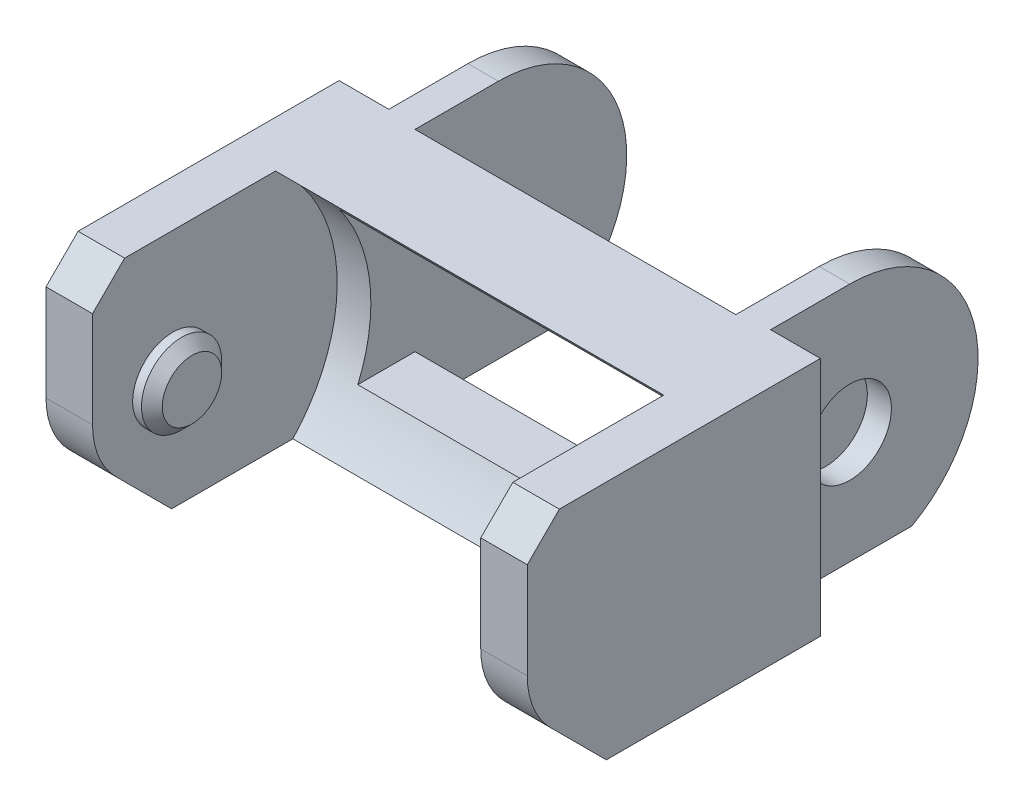
SolidWorks part; units mm, degrees
ref_plane "前基準面" through (0, 0, 0) normal (0, 0, 1) x (1, 0, 0)
ref_plane "上基準面" through (0, 0, 0) normal (0, 1, 0) x (1, 0, 0)
ref_plane "右基準面" through (0, 0, 0) normal (1, 0, 0) x (0, 0, -1)
sketch "草圖1" plane through (0, 0, 0) normal (0, 0, 1) x (1, 0, 0)
  line L1 (-12.751, 5.0503) -> (17.249, 5.0503)
  line L2 (-12.751, 5.0503) -> (-12.751, -9.9497)
  line L3 (-12.751, -9.9497) -> (17.249, -9.9497)
  line L4 (17.249, 5.0503) -> (17.249, -9.9497)
  dimension "D1" = 30
  dimension "D2" = 15
extrude "填料-伸長1" add sketch "草圖1" along normal blind 18
sketch "草圖2" plane through (0, 0, 18) normal (0, 0, 1) x (1, 0, 0)
  line L0 (-12.751, 5.0503) -> (-12.751, -9.9497) construction
  line L1 (-7.751, 3.0503) -> (12.249, 3.0503)
  line L2 (-7.751, 3.0503) -> (-7.751, -6.9497)
  line L3 (-7.751, -6.9497) -> (12.249, -6.9497)
  line L4 (12.249, 3.0503) -> (12.249, -6.9497)
  line L5 (17.249, -9.9497) -> (17.249, 5.0503) construction
  line L6 (17.249, 5.0503) -> (-12.751, 5.0503) construction
  line L7 (-12.751, -9.9497) -> (17.249, -9.9497) construction
  dimension "D1" = 5
  dimension "D2" = 5
  dimension "D3" = 2
  dimension "D4" = 3
extrude "除料-伸長1" cut sketch "草圖2" against normal up to next
sketch "草圖3" plane through (0, -6.9497, 0) normal (0, 1, 0) x (1, 0, 0)
  line L0 (-7.751, 0) -> (-7.751, -18) construction
  line L1 (-7.751, -6) -> (12.249, -6)
  line L2 (-7.751, -6) -> (-7.751, -18)
  line L3 (-7.751, -18) -> (12.249, -18)
  line L4 (12.249, -6) -> (12.249, -18)
  dimension "D1" = 12
extrude "除料-伸長2" cut sketch "草圖3" against normal up to next
sketch "草圖4" plane through (-7.751, 0, 0) normal (1, 0, 0) x (0, 0, -1)
  line L0 (-18, 3.0503) -> (-18, -9.9497) construction
  line L1 (-18, -9.9497) -> (-6, -9.9497) construction
  line L3 (-13, -2.9497) -> (-18, -2.9497)
  line L4 (-13, -2.9497) -> (-13, 7.8945)
  line L5 (-18, -2.9497) -> (-18, 7.8945)
  line L6 (-13, 7.8945) -> (-18, 7.8945)
  circle A0 centre (-13, -2.9497) radius 10.25
  line M3 (0, 3.0503) -> (-18, 3.0503)
  line M4 (-18, 3.0503) -> (-18, -9.9497)
  line M5 (-18, -9.9497) -> (-6, -9.9497)
  line M6 (-6, -9.9497) -> (-6, -6.9497)
  line M7 (-6, -6.9497) -> (0, -6.9497)
  dimension "D2" = 7
  dimension "D3" = 20.5
  dimension "D1" = 5
extrude "除料-伸長5" cut sketch "草圖4" against normal blind 2.1 and the other way blind 22.1 contours L3 L4 M3 M4 | A0 L4 L3 M7 M3 M4 M5 M6 | A0 L4 L6 L5 | A0 L4 M3 | L4 A0 L5 M3 | L5 A0 M7 M6 M5 M4 region at (-7.751, -3.92, 9.9772) region at (-7.751, 0.0503, 15.5) region at (-7.751, -6.4497, 18.275) region at (-7.751, 4.9834, 15.3602) region at (-7.751, 4.7846, 9.7748) region at (-7.751, 7.3136, 16.0262)
sketch "草圖5" plane through (14.349, 0, 0) normal (-1, 0, 0) x (0, 0, 1)
  circle A0 centre (13, -2.9497) radius 2.5
  arc A2 (6.592, 5.0503) -> (5.5125, -9.9497) centre (13, -2.9497) ccw construction
  dimension "D1" = 5
extrude "填料-伸長2" add sketch "草圖5" along normal blind 1.2
sketch "草圖6" plane through (-9.851, 0, 0) normal (1, 0, 0) x (0, 0, -1)
  circle A0 centre (-13, -2.9497) radius 2.5
  arc A1 (-5.5125, -9.9497) -> (-6.592, 5.0503) centre (-13, -2.9497) ccw construction
  dimension "D1" = 5
extrude "填料-伸長3" add sketch "草圖6" along normal blind 1.2
chamfer "導角1" distance 0.65 angle 45 2 edges at (-8.651, -0.4497, 13) (13.149, -5.4497, 13)
sketch "草圖7" plane through (-9.851, 0, 0) normal (1, 0, 0) x (0, 0, -1)
  line L0 (-13.0711, -9.9497) -> (-18, -5.0208)
  line L1 (-18, -9.9497) -> (-5.5125, -9.9497) construction
  line L2 (-18, -9.9497) -> (-18, 5.0503) construction
  circle A0 centre (-13, -2.9497) radius 2.5 construction
  line M4 (-18, 5.0503) -> (-18, -9.9497)
  line M5 (-18, -9.9497) -> (-5.5125, -9.9497)
  dimension "D1" = 45
  dimension "D2" = 5
extrude "除料-伸長6" cut sketch "草圖7" against normal through all both and the other way through all contours L0 M5 M4 region at (-9.851, -8.3067, 16.357)
sketch "草圖8" plane through (-9.851, 0, 0) normal (1, 0, 0) x (0, 0, -1)
  line L0 (-18, -5.0208) -> (-18, -2.9497)
  line L1 (-18, -5.0208) -> (-15.5355, -7.4853)
  line L2 (-13.0711, -9.9497) -> (-18, -5.0208) construction
  circle A0 centre (-13, -2.9497) radius 5
  line M1 (-18, -5.0208) -> (-13.0711, -9.9497)
  line M5 (-18, 5.0503) -> (-18, -5.0208)
extrude "除料-伸長7" cut sketch "草圖8" against normal through all both and the other way through all contours A0 M5 M1 region at (-9.851, -4.8962, 17.6992)
sketch "草圖9" plane through (0, 0, 0) normal (0, 0, -1) x (-1, 0, 0)
  line L0 (-17.249, 5.0503) -> (12.751, 5.0503) construction
  line L1 (-12.249, 5.0503) -> (7.751, 5.0503)
  line L2 (-12.249, 5.0503) -> (-12.249, -9.9497)
  line L3 (-12.249, -9.9497) -> (7.751, -9.9497)
  line L4 (7.751, 5.0503) -> (7.751, -9.9497)
  line L5 (12.751, -9.9497) -> (-17.249, -9.9497) construction
  line L6 (-12.249, 3.0503) -> (-12.249, -6.9497) construction
  line L7 (9.651, -9.9497) -> (-14.149, -9.9497)
  line L8 (9.651, -9.9497) -> (9.651, 5.0503)
  line L9 (9.651, 5.0503) -> (-14.149, 5.0503)
  line L10 (-14.149, -9.9497) -> (-14.149, 5.0503)
  line L11 (7.751, -6.9497) -> (7.751, 3.0503) construction
  line M6 (7.751, 3.0503) -> (7.751, -6.9497)
  line M8 (-12.249, -6.9497) -> (-12.249, 3.0503)
  line M10 (12.751, 5.0503) -> (-17.249, 5.0503)
  line M12 (-17.249, -9.9497) -> (12.751, -9.9497)
  dimension "D1" = 1.9
  dimension "D2" = 1.9
extrude "填料-伸長4" add sketch "草圖9" along normal blind 20 contours L8 L4 M12 M10 M6 | L10 L2 M12 M8 M10 region at (13.199, -2.4497, 0) region at (-8.701, -2.4497, 0)
sketch "草圖10" plane through (14.149, 0, 0) normal (1, 0, 0) x (0, 0, -1)
  line L0 (0, -9.9497) -> (0, 5.0503) construction
  line L1 (20, -9.9497) -> (0, -9.9497) construction
  circle A0 centre (5.2, -2.9497) radius 2.6
  dimension "D1" = 5.2
  dimension "D2" = 5.2
  dimension "D3" = 7
extrude "除料-伸長8" cut sketch "草圖10" against normal through all
sketch "草圖12" plane through (14.149, 0, 0) normal (1, 0, 0) x (0, 0, -1)
  line L1 (5.2, 5.0503) -> (18.304, 5.0503)
  line L2 (5.2, 5.0503) -> (5.2, -15.4926)
  line L3 (5.2, -15.4926) -> (18.304, -15.4926)
  line L4 (18.304, 5.0503) -> (18.304, -15.4926)
  circle A0 centre (5.2, -2.9497) radius 8
  line M3 (0, -9.9497) -> (20, -9.9497)
  line M4 (20, -9.9497) -> (20, 5.0503)
  line M5 (20, 5.0503) -> (0, 5.0503)
extrude "除料-伸長9" cut sketch "草圖12" against normal through all both and the other way through all contours A0 L4 M3 M5 | L4 M5 M3 M4 region at (14.149, -2.1497, -14.8341) region at (14.149, -2.4497, -19.152)
sketch "草圖15" plane through (12.249, 0, 0) normal (1, 0, 0) x (0, 0, -1)
  circle A0 centre (5.2, -2.9497) radius 2.6
extrude "填料-伸長6" add sketch "草圖15" along normal blind 0.4
sketch "草圖16" plane through (-7.751, 0, 0) normal (-1, 0, 0) x (0, 0, 1)
  circle A0 centre (-5.2, -2.9497) radius 2.6
extrude "填料-伸長7" add sketch "草圖16" along normal blind 0.4
chamfer "導角2" distance 2 angle 45 2 edges at (15.799, 5.0503, 18) (-11.301, 5.0503, 18)
sketch "草圖17" plane through (0, 0, 0) normal (0, 0, -1) x (-1, 0, 0)
  line L1 (-17.249, 5.0503) -> (-14.149, 5.0503)
  line L2 (-17.249, 5.0503) -> (-17.249, -9.9497)
  line L3 (-17.249, -9.9497) -> (-14.149, -9.9497)
  line L4 (-14.149, 5.0503) -> (-14.149, -9.9497)
  line L5 (9.651, 5.0503) -> (12.751, 5.0503)
  line L6 (9.651, 5.0503) -> (9.651, -9.9497)
  line L7 (9.651, -9.9497) -> (12.751, -9.9497)
  line L8 (12.751, 5.0503) -> (12.751, -9.9497)
extrude "填料-伸長8" add sketch "草圖17" along normal blind 0.27
